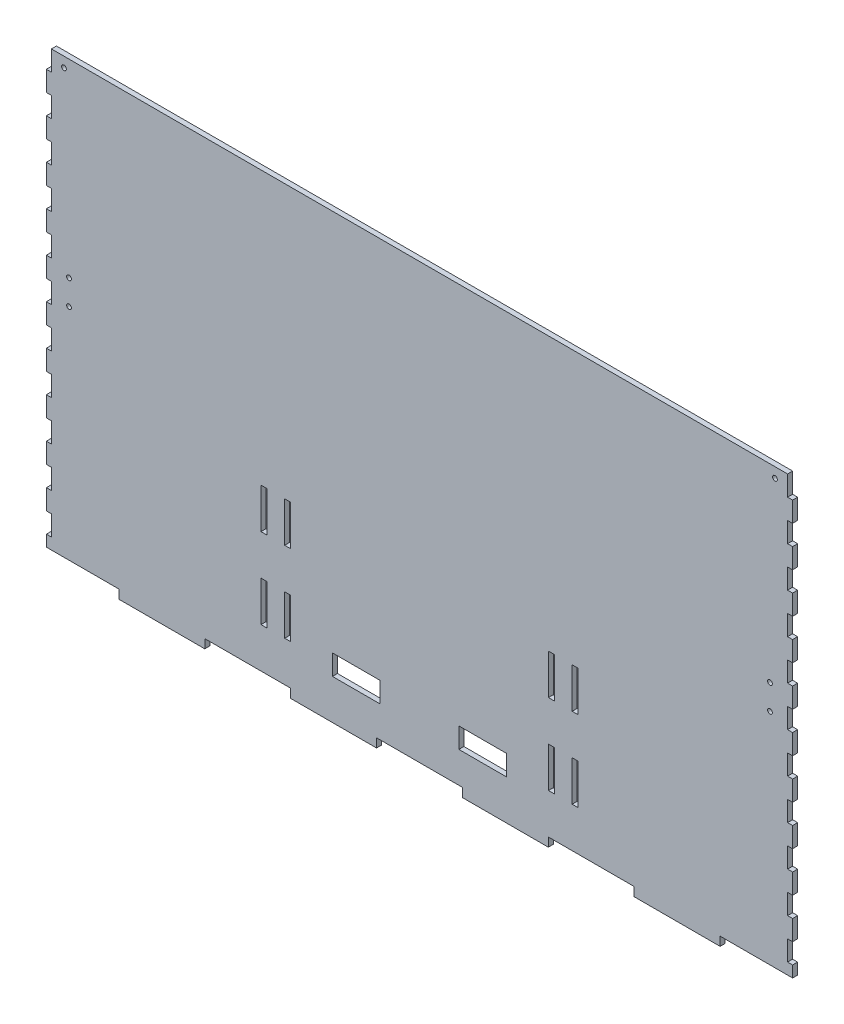
SolidWorks part; units mm, degrees
material "Acrylic (Medium-high impact)"
ref_plane "Front Plane" through (0, 0, 0) normal (0, 0, 1) x (1, 0, 0)
ref_plane "Top Plane" through (0, 0, 0) normal (0, 1, 0) x (1, 0, 0)
ref_plane "Right Plane" through (0, 0, 0) normal (1, 0, 0) x (0, 0, -1)
sketch "Sketch1" plane through (0, 0, 0) normal (0, 0, 1) x (1, 0, 0)
  line L0 (0, 139.7) -> (0, -139.7) construction
  line L1 (-406.4, 139.7) -> (406.4, 139.7)
  line L2 (-406.4, 139.7) -> (-406.4, -139.7)
  line L3 (-406.4, -139.7) -> (406.4, -139.7)
  line L4 (406.4, 139.7) -> (406.4, -139.7)
  line L49 (-381, 127) -> (-381, 114.3)
  line L54 (-381, 139.7) -> (-377.825, 139.7)
  line L55 (-381, 139.7) -> (-381, 127)
  line L56 (-381, 127) -> (-377.825, 127)
  line L57 (-377.825, 139.7) -> (-377.825, 127)
  line L58 (-381, 127) -> (-377.825, 127)
  line L59 (-377.825, 127) -> (-377.825, 114.3)
  line L60 (-381, 114.3) -> (-377.825, 114.3)
  line L61 (-381, 114.3) -> (-381, 101.6)
  line L62 (-381, 114.3) -> (-377.825, 114.3)
  line L63 (-377.825, 114.3) -> (-377.825, 101.6)
  line L64 (-381, 101.6) -> (-377.825, 101.6)
  line L65 (-381, 101.6) -> (-381, 88.9)
  line L66 (-381, 101.6) -> (-377.825, 101.6)
  line L67 (-377.825, 101.6) -> (-377.825, 88.9)
  line L68 (-381, 88.9) -> (-377.825, 88.9)
  line L69 (-381, 88.9) -> (-381, 76.2)
  line L70 (-381, 88.9) -> (-377.825, 88.9)
  line L71 (-377.825, 88.9) -> (-377.825, 76.2)
  line L72 (-381, 76.2) -> (-377.825, 76.2)
  line L73 (-381, 76.2) -> (-381, 63.5)
  line L74 (-381, 76.2) -> (-377.825, 76.2)
  line L75 (-377.825, 76.2) -> (-377.825, 63.5)
  line L76 (-381, 63.5) -> (-377.825, 63.5)
  line L77 (-381, 63.5) -> (-381, 50.8)
  line L78 (-381, 63.5) -> (-377.825, 63.5)
  line L79 (-377.825, 63.5) -> (-377.825, 50.8)
  line L80 (-381, 50.8) -> (-377.825, 50.8)
  line L81 (-381, 50.8) -> (-381, 38.1)
  line L82 (-381, 50.8) -> (-377.825, 50.8)
  line L83 (-377.825, 50.8) -> (-377.825, 38.1)
  line L84 (-381, 38.1) -> (-377.825, 38.1)
  line L85 (-381, 38.1) -> (-381, 25.4)
  line L86 (-381, 38.1) -> (-377.825, 38.1)
  line L87 (-377.825, 38.1) -> (-377.825, 25.4)
  line L88 (-381, 25.4) -> (-377.825, 25.4)
  line L89 (377.825, 127) -> (377.825, 114.3)
  line L90 (377.825, 139.7) -> (381, 139.7)
  line L91 (377.825, 139.7) -> (377.825, 127)
  line L92 (377.825, 127) -> (381, 127)
  line L93 (381, 139.7) -> (381, 127)
  line L94 (377.825, 127) -> (381, 127)
  line L95 (381, 127) -> (381, 114.3)
  line L96 (377.825, 114.3) -> (381, 114.3)
  line L97 (377.825, 114.3) -> (377.825, 101.6)
  line L98 (377.825, 114.3) -> (381, 114.3)
  line L99 (381, 114.3) -> (381, 101.6)
  line L100 (377.825, 101.6) -> (381, 101.6)
  line L101 (377.825, 101.6) -> (377.825, 88.9)
  line L102 (377.825, 101.6) -> (381, 101.6)
  line L103 (381, 101.6) -> (381, 88.9)
  line L104 (377.825, 88.9) -> (381, 88.9)
  line L105 (377.825, 88.9) -> (377.825, 76.2)
  line L106 (377.825, 88.9) -> (381, 88.9)
  line L107 (381, 88.9) -> (381, 76.2)
  line L108 (377.825, 76.2) -> (381, 76.2)
  line L109 (377.825, 76.2) -> (377.825, 63.5)
  line L110 (377.825, 76.2) -> (381, 76.2)
  line L111 (381, 76.2) -> (381, 63.5)
  line L112 (377.825, 63.5) -> (381, 63.5)
  line L113 (377.825, 63.5) -> (377.825, 50.8)
  line L114 (377.825, 63.5) -> (381, 63.5)
  line L115 (381, 63.5) -> (381, 50.8)
  line L116 (377.825, 50.8) -> (381, 50.8)
  line L117 (377.825, 50.8) -> (377.825, 38.1)
  line L118 (377.825, 50.8) -> (381, 50.8)
  line L119 (381, 50.8) -> (381, 38.1)
  line L120 (377.825, 38.1) -> (381, 38.1)
  line L121 (377.825, 38.1) -> (377.825, 25.4)
  line L122 (377.825, 38.1) -> (381, 38.1)
  line L123 (381, 38.1) -> (381, 25.4)
  line L124 (377.825, 25.4) -> (381, 25.4)
  line L125 (-352.2133, -134.112) -> (-352.2133, -139.7)
  line L126 (-406.4, -134.112) -> (-352.2133, -134.112)
  line L127 (-406.4, -134.112) -> (-406.4, -139.7)
  line L128 (-406.4, -139.7) -> (-352.2133, -139.7)
  line L129 (-352.2133, -134.112) -> (-352.2133, -139.7)
  line L130 (-352.2133, -134.112) -> (-298.0267, -134.112)
  line L131 (-298.0267, -134.112) -> (-298.0267, -139.7)
  line L132 (-352.2133, -139.7) -> (-298.0267, -139.7)
  line L133 (-298.0267, -134.112) -> (-298.0267, -139.7)
  line L134 (-298.0267, -134.112) -> (-243.84, -134.112)
  line L135 (-243.84, -134.112) -> (-243.84, -139.7)
  line L136 (-298.0267, -139.7) -> (-243.84, -139.7)
  line L137 (-243.84, -134.112) -> (-243.84, -139.7)
  line L138 (-243.84, -134.112) -> (-189.6533, -134.112)
  line L139 (-189.6533, -134.112) -> (-189.6533, -139.7)
  line L140 (-243.84, -139.7) -> (-189.6533, -139.7)
  line L141 (-189.6533, -134.112) -> (-189.6533, -139.7)
  line L142 (-189.6533, -134.112) -> (-135.4667, -134.112)
  line L143 (-135.4667, -134.112) -> (-135.4667, -139.7)
  line L144 (-189.6533, -139.7) -> (-135.4667, -139.7)
  line L145 (-135.4667, -134.112) -> (-135.4667, -139.7)
  line L146 (-135.4667, -134.112) -> (-81.28, -134.112)
  line L147 (-81.28, -134.112) -> (-81.28, -139.7)
  line L148 (-135.4667, -139.7) -> (-81.28, -139.7)
  line L149 (-81.28, -134.112) -> (-81.28, -139.7)
  line L150 (-81.28, -134.112) -> (-27.0933, -134.112)
  line L151 (-27.0933, -134.112) -> (-27.0933, -139.7)
  line L152 (-81.28, -139.7) -> (-27.0933, -139.7)
  line L153 (-27.0933, -134.112) -> (-27.0933, -139.7)
  line L154 (-27.0933, -134.112) -> (27.0933, -134.112)
  line L155 (27.0933, -134.112) -> (27.0933, -139.7)
  line L156 (-27.0933, -139.7) -> (27.0933, -139.7)
  line L157 (27.0933, -134.112) -> (27.0933, -139.7)
  line L158 (27.0933, -134.112) -> (81.28, -134.112)
  line L159 (81.28, -134.112) -> (81.28, -139.7)
  line L160 (27.0933, -139.7) -> (81.28, -139.7)
  line L161 (81.28, -134.112) -> (81.28, -139.7)
  line L162 (81.28, -134.112) -> (135.4667, -134.112)
  line L163 (135.4667, -134.112) -> (135.4667, -139.7)
  line L164 (81.28, -139.7) -> (135.4667, -139.7)
  line L165 (135.4667, -134.112) -> (135.4667, -139.7)
  line L166 (135.4667, -134.112) -> (189.6533, -134.112)
  line L167 (189.6533, -134.112) -> (189.6533, -139.7)
  line L168 (135.4667, -139.7) -> (189.6533, -139.7)
  line L169 (189.6533, -134.112) -> (189.6533, -139.7)
  line L170 (189.6533, -134.112) -> (243.84, -134.112)
  line L171 (243.84, -134.112) -> (243.84, -139.7)
  line L172 (189.6533, -139.7) -> (243.84, -139.7)
  line L173 (243.84, -134.112) -> (243.84, -139.7)
  line L174 (243.84, -134.112) -> (298.0267, -134.112)
  line L175 (298.0267, -134.112) -> (298.0267, -139.7)
  line L176 (243.84, -139.7) -> (298.0267, -139.7)
  line L177 (298.0267, -134.112) -> (298.0267, -139.7)
  line L178 (298.0267, -134.112) -> (352.2133, -134.112)
  line L179 (352.2133, -134.112) -> (352.2133, -139.7)
  line L180 (298.0267, -139.7) -> (352.2133, -139.7)
  line L181 (352.2133, -134.112) -> (352.2133, -139.7)
  line L182 (352.2133, -134.112) -> (406.4, -134.112)
  line L183 (406.4, -134.112) -> (406.4, -139.7)
  line L184 (352.2133, -139.7) -> (406.4, -139.7)
  line L205 (-90.678, 84.5227) -> (-90.678, -139.7) construction
  line L206 (90.678, 84.5227) -> (90.678, -139.7) construction
  line L207 (-90.678, -27.5886) -> (90.678, -27.5886) construction
  line L208 (-381, 25.4) -> (-381, 12.7)
  line L209 (-381, 25.4) -> (-377.825, 25.4)
  line L210 (-377.825, 25.4) -> (-377.825, 12.7)
  line L211 (-381, 12.7) -> (-377.825, 12.7)
  line L212 (-381, 12.7) -> (-381, 0)
  line L213 (-381, 12.7) -> (-377.825, 12.7)
  line L214 (-377.825, 12.7) -> (-377.825, 0)
  line L215 (-381, 0) -> (-377.825, 0)
  line L224 (-377.825, 0) -> (377.825, 0) construction
  line L229 (377.825, 25.4) -> (377.825, 12.7)
  line L230 (377.825, 25.4) -> (381, 25.4)
  line L231 (381, 25.4) -> (381, 12.7)
  line L232 (377.825, 12.7) -> (381, 12.7)
  line L233 (377.825, 12.7) -> (377.825, 0)
  line L234 (377.825, 12.7) -> (381, 12.7)
  line L235 (381, 12.7) -> (381, 0)
  line L236 (377.825, 0) -> (381, 0)
  line L237 (-381, 0) -> (-381, -12.7)
  line L238 (-381, 0) -> (-377.825, 0)
  line L239 (-377.825, 0) -> (-377.825, -12.7)
  line L240 (-381, -12.7) -> (-377.825, -12.7)
  line L241 (-381, -12.7) -> (-381, -25.4)
  line L242 (-381, -12.7) -> (-377.825, -12.7)
  line L243 (-377.825, -12.7) -> (-377.825, -25.4)
  line L244 (-381, -25.4) -> (-377.825, -25.4)
  line L245 (-381, -25.4) -> (-381, -38.1)
  line L246 (-381, -25.4) -> (-377.825, -25.4)
  line L247 (-377.825, -25.4) -> (-377.825, -38.1)
  line L248 (-381, -38.1) -> (-377.825, -38.1)
  line L249 (-381, -38.1) -> (-381, -50.8)
  line L250 (-381, -38.1) -> (-377.825, -38.1)
  line L251 (-377.825, -38.1) -> (-377.825, -50.8)
  line L252 (-381, -50.8) -> (-377.825, -50.8)
  line L253 (-381, -50.8) -> (-381, -63.5)
  line L254 (-381, -50.8) -> (-377.825, -50.8)
  line L255 (-377.825, -50.8) -> (-377.825, -63.5)
  line L256 (-381, -63.5) -> (-377.825, -63.5)
  line L257 (-381, -63.5) -> (-381, -76.2)
  line L258 (-381, -63.5) -> (-377.825, -63.5)
  line L259 (-377.825, -63.5) -> (-377.825, -76.2)
  line L260 (-381, -76.2) -> (-377.825, -76.2)
  line L261 (-381, -76.2) -> (-381, -88.9)
  line L262 (-381, -76.2) -> (-377.825, -76.2)
  line L263 (-377.825, -76.2) -> (-377.825, -88.9)
  line L264 (-381, -88.9) -> (-377.825, -88.9)
  line L265 (-381, -88.9) -> (-381, -101.6)
  line L266 (-381, -88.9) -> (-377.825, -88.9)
  line L267 (-377.825, -88.9) -> (-377.825, -101.6)
  line L268 (-381, -101.6) -> (-377.825, -101.6)
  line L269 (-381, -101.6) -> (-381, -114.3)
  line L270 (-381, -101.6) -> (-377.825, -101.6)
  line L271 (-377.825, -101.6) -> (-377.825, -114.3)
  line L272 (-381, -114.3) -> (-377.825, -114.3)
  line L273 (-381, -114.3) -> (-381, -127)
  line L274 (-381, -114.3) -> (-377.825, -114.3)
  line L275 (-377.825, -114.3) -> (-377.825, -127)
  line L276 (-381, -127) -> (-377.825, -127)
  line L277 (-381, -127) -> (-381, -139.7)
  line L278 (-381, -127) -> (-377.825, -127)
  line L279 (-377.825, -127) -> (-377.825, -139.7)
  line L280 (-381, -139.7) -> (-377.825, -139.7)
  line L281 (377.825, 0) -> (377.825, -12.7)
  line L282 (377.825, 0) -> (381, 0)
  line L283 (381, 0) -> (381, -12.7)
  line L284 (377.825, -12.7) -> (381, -12.7)
  line L285 (377.825, -12.7) -> (377.825, -25.4)
  line L286 (377.825, -12.7) -> (381, -12.7)
  line L287 (381, -12.7) -> (381, -25.4)
  line L288 (377.825, -25.4) -> (381, -25.4)
  line L289 (377.825, -25.4) -> (377.825, -38.1)
  line L290 (377.825, -25.4) -> (381, -25.4)
  line L291 (381, -25.4) -> (381, -38.1)
  line L292 (377.825, -38.1) -> (381, -38.1)
  line L293 (377.825, -38.1) -> (377.825, -50.8)
  line L294 (377.825, -38.1) -> (381, -38.1)
  line L295 (381, -38.1) -> (381, -50.8)
  line L296 (377.825, -50.8) -> (381, -50.8)
  line L297 (377.825, -50.8) -> (377.825, -63.5)
  line L298 (377.825, -50.8) -> (381, -50.8)
  line L299 (381, -50.8) -> (381, -63.5)
  line L300 (377.825, -63.5) -> (381, -63.5)
  line L301 (377.825, -63.5) -> (377.825, -76.2)
  line L302 (377.825, -63.5) -> (381, -63.5)
  line L303 (381, -63.5) -> (381, -76.2)
  line L304 (377.825, -76.2) -> (381, -76.2)
  line L305 (377.825, -76.2) -> (377.825, -88.9)
  line L306 (377.825, -76.2) -> (381, -76.2)
  line L307 (381, -76.2) -> (381, -88.9)
  line L308 (377.825, -88.9) -> (381, -88.9)
  line L309 (377.825, -88.9) -> (377.825, -101.6)
  line L310 (377.825, -88.9) -> (381, -88.9)
  line L311 (381, -88.9) -> (381, -101.6)
  line L312 (377.825, -101.6) -> (381, -101.6)
  line L313 (377.825, -101.6) -> (377.825, -114.3)
  line L314 (377.825, -101.6) -> (381, -101.6)
  line L315 (381, -101.6) -> (381, -114.3)
  line L316 (377.825, -114.3) -> (381, -114.3)
  line L317 (377.825, -114.3) -> (377.825, -127)
  line L318 (377.825, -114.3) -> (381, -114.3)
  line L319 (381, -114.3) -> (381, -127)
  line L320 (377.825, -127) -> (381, -127)
  line L321 (377.825, -127) -> (377.825, -139.7)
  line L322 (377.825, -127) -> (381, -127)
  line L323 (381, -127) -> (381, -139.7)
  line L324 (377.825, -139.7) -> (381, -139.7)
  point P6 (0, 0)
  point P128 (0, -27.5886)
  point P153 (0, 0)
  dimension "D4" = 12.7
  dimension "D5" = 3.175
  dimension "D10" = 181.356
  dimension "D12" = 755.65
  dimension "D8" = 812.8
  dimension "D11" = 54.1867
  dimension "D2" = 273.812
  dimension "D9" = 279.4
  dimension "D3" = 22
  dimension "D7" = 15
  dimension "D6" = 22
extrude "Main Extrude" add sketch "Sketch1" along normal blind 3.175 contours L321 L317 L313 L309 L305 L301 L297 L293 L289 L285 L281 L233 L229 L121 L117 L113 L109 L105 L101 L97 L89 L91 L1 L57 L59 L63 L67 L71 L75 L79 L83 L87 L210 L214 L239 L243 L247 L251 L255 L259 L263 L267 L271 L275 L279 L126 L130 L134 L138 L142 L146 | L277 L273 L269 L265 L261 L257 L253 L249 L245 L241 L237 L212 L208 L85 L81 L77 L73 L69 L65 L61 L49 L55 L1 L2 L126 | L319 L323 L182 L4 L1 L93 L95 L99 L103 L107 L111 L115 L119 L123 L231 L235 L283 L287 L291 L295 L299 L303 L307 L311 L315 | L126 L279 L3 L125 | L135 L134 L131 L3 | L143 L142 L139 L3 | L151 L150 L147 L3 | L159 L158 L155 L3 | L167 L166 L163 L3 | L175 L174 L171 L3 | L323 L182 L321 L184 | L89 L96 L95 L92 | L101 L104 L103 L100 | L109 L112 L111 L108 | L117 L120 L119 L116 | L229 L232 L231 L124 | L281 L284 L283 L236 | L289 L292 L291 L288 | L297 L300 L299 L296 | L305 L308 L307 L304 | L313 L316 L315 L312 | L323 L320 L321 L182 | L49 L60 L59 L56 | L65 L68 L67 L64 | L73 L76 L75 L72 | L81 L84 L83 L80 | L208 L211 L210 L88 | L237 L240 L239 L215 | L245 L248 L247 L244 | L253 L256 L255 L252 | L261 L264 L263 L260 | L269 L272 L271 L268 | L279 L276 L277 L126 | L277 L126 L2 L3 | L321 L182 L179 L3 | L182 L323 L3 L4 | L279 L126 L277 L128 region at (-393.7, 2.794, 0) region at (-393.7, -136.906, 0) region at (0, 2.794, 0) region at (-379.4125, 120.65, 0) region at (-379.4125, -130.556, 0) region at (-379.4125, -136.906, 0) region at (-365.0192, -136.906, 0) region at (393.7, 2.794, 0) region at (379.4125, 120.65, 0) region at (-379.4125, 95.25, 0) region at (-379.4125, -107.95, 0) region at (-270.9333, -136.906, 0) region at (393.7, -136.906, 0) region at (379.4125, 95.25, 0) region at (-379.4125, 69.85, 0) region at (-379.4125, -82.55, 0) region at (379.4125, -136.906, 0) region at (379.4125, -130.556, 0) region at (-162.56, -136.906, 0) region at (365.0192, -136.906, 0) region at (379.4125, 69.85, 0) region at (-379.4125, 44.45, 0) region at (-379.4125, -57.15, 0) region at (379.4125, -107.95, 0) region at (-54.1867, -136.906, 0) region at (270.9333, -136.906, 0) region at (379.4125, 44.45, 0) region at (-379.4125, 19.05, 0) region at (-379.4125, -31.75, 0) region at (379.4125, -82.55, 0) region at (54.1867, -136.906, 0) region at (162.56, -136.906, 0) region at (379.4125, 19.05, 0) region at (-379.4125, -6.35, 0) region at (379.4125, -57.15, 0) region at (379.4125, -6.35, 0) region at (379.4125, -31.75, 0)
sketch "Sketch8" plane through (0, 0, 3.175) normal (0, 0, 1) x (1, 0, 0)
  line L0 (-406.4, 139.7) -> (-406.4, -139.7) construction
  line L1 (-381, 28.2575) -> (-384.175, 28.2575)
  line L2 (-381, 28.2575) -> (-381, -3.6195)
  line L3 (-381, -3.6195) -> (-384.175, -3.6195)
  line L4 (-384.175, 28.2575) -> (-384.175, -3.6195)
  line L5 (-406.4, -139.7) -> (-352.2133, -139.7) construction
  line L6 (381, 28.2575) -> (384.175, 28.2575)
  line L7 (381, 28.2575) -> (381, -3.6195)
  line L8 (381, -3.6195) -> (384.175, -3.6195)
  line L9 (384.175, 28.2575) -> (384.175, -3.6195)
  line L11 (-381, 88.9) -> (-381, 76.2) construction
  line L12 (-352.2133, -134.112) -> (-298.0267, -134.112) construction
  line L13 (381, 88.9) -> (381, 76.2) construction
  line L14 (-393.7, -120.65) -> (393.7, -120.65) construction
  circle A0 centre (-393.7, -120.65) radius 1.5
  circle A1 centre (393.7, -120.65) radius 1.5
  point P6 (0, -120.65)
  point P16 (-384.175, 12.319)
  dimension "D5" = 3
  dimension "D1" = 31.877
  dimension "D2" = 3.175
  dimension "D3" = 146.431
  dimension "D4" = 19.05
  dimension "D6" = 12.7
extrude "Mount Holes" cut sketch "Sketch8" against normal through all
sketch "Sketch3" plane through (0, 0, 3.175) normal (0, 0, 1) x (1, 0, 0)
  line L0 (-135.4667, -134.112) -> (-81.28, -134.112) construction
  line L1 (-96.52, 126.492) -> (-84.836, 126.492)
  line L2 (-96.52, 126.492) -> (-96.52, -134.112)
  line L3 (-96.52, -134.112) -> (-84.836, -134.112)
  line L4 (-84.836, 126.492) -> (-84.836, -134.112)
  line L5 (81.28, -134.112) -> (135.4667, -134.112) construction
  line L6 (84.836, 126.492) -> (96.52, 126.492)
  line L7 (84.836, 126.492) -> (84.836, -134.112)
  line L8 (84.836, -134.112) -> (96.52, -134.112)
  line L9 (96.52, 126.492) -> (96.52, -134.112)
  line L10 (-84.836, -3.81) -> (84.836, -3.81) construction
  line L12 (-106.553, 10.3505) -> (-74.803, 10.3505)
  line L13 (-106.553, 10.3505) -> (-106.553, 0.8255)
  line L14 (-106.553, 0.8255) -> (-74.803, 0.8255)
  line L15 (-74.803, 10.3505) -> (-74.803, 0.8255)
  line L16 (74.803, 10.3505) -> (106.553, 10.3505)
  line L17 (74.803, 10.3505) -> (74.803, 0.8255)
  line L18 (74.803, 0.8255) -> (106.553, 0.8255)
  line L19 (106.553, 10.3505) -> (106.553, 0.8255)
  line L20 (-96.52, 126.492) -> (-92.6465, 126.492)
  line L21 (-96.52, 126.492) -> (-96.52, 82.042)
  line L22 (-96.52, 82.042) -> (-92.6465, 82.042)
  line L23 (-92.6465, 126.492) -> (-92.6465, 82.042)
  line L24 (-84.836, 126.492) -> (-88.7095, 126.492)
  line L25 (-84.836, 126.492) -> (-84.836, 82.042)
  line L26 (-84.836, 82.042) -> (-88.7095, 82.042)
  line L27 (-88.7095, 126.492) -> (-88.7095, 82.042)
  line L28 (84.836, 126.492) -> (88.7095, 126.492)
  line L29 (84.836, 126.492) -> (84.836, 82.042)
  line L30 (84.836, 82.042) -> (88.7095, 82.042)
  line L31 (88.7095, 126.492) -> (88.7095, 82.042)
  line L32 (96.52, 126.492) -> (92.6465, 126.492)
  line L33 (96.52, 126.492) -> (96.52, 82.042)
  line L34 (96.52, 82.042) -> (92.6465, 82.042)
  line L35 (92.6465, 126.492) -> (92.6465, 82.042)
  point P14 (-90.678, 126.492)
  point P15 (90.678, 126.492)
  point P16 (0, -3.81)
  point P27 (-90.678, 10.3505)
  point P28 (90.678, 10.3505)
  point P29 (-74.803, 5.588)
  dimension "D1" = 11.684
  dimension "D2" = 260.604
  dimension "D3" = 181.356
  dimension "D4" = 9.525
  dimension "D5" = 139.7
  dimension "D6" = 31.75
  dimension "D8" = 3.937
  dimension "D7" = 44.45
extrude "Door Slots" [suppressed] cut sketch "Sketch3" against normal through all contours L2 L12 L4 L1 | L2 L14 L4 L12 | L15 L12 L4 L14 | L13 L14 L2 L12 | L14 L2 L3 L4 | L7 L16 L9 L6 | L7 L18 L9 L16 | L19 L16 L9 L18 | L17 L18 L7 L16 | L18 L7 L8 L9
sketch "Sketch4" plane through (0, 0, 0) normal (0, 0, 1) x (1, 0, 0)
  line L1 (-81.28, -139.7) -> (-27.0933, -139.7) construction
  line L2 (-55.48, -112.41) -> (-52.178, -112.41)
  line L3 (-52.178, -112.41) -> (-52.178, -106.172)
  line L4 (-52.178, -106.172) -> (-2.178, -106.172)
  line L5 (-2.178, -106.172) -> (-2.178, -112.41)
  line L6 (-2.178, -112.41) -> (1.124, -112.41)
  line L9 (-55.48, -112.41) -> (-55.48, -134.112)
  line L10 (-55.48, -134.112) -> (-52.178, -134.112)
  line L11 (-52.178, -134.112) -> (-52.178, -139.7)
  line L12 (1.124, -112.41) -> (1.124, -134.112)
  line L13 (1.124, -134.112) -> (-2.178, -134.112)
  line L14 (-2.178, -134.112) -> (-2.178, -139.7)
  line L15 (-52.178, -139.7) -> (-2.178, -139.7)
  line L16 (-27.0933, -134.112) -> (27.0933, -134.112) construction
  line L17 (-27.0933, -134.112) -> (27.0933, -134.112) construction
  line L18 (12.128, -101.642) -> (42.228, -101.642)
  line L19 (12.128, -101.642) -> (12.128, -114.492)
  line L20 (12.128, -114.492) -> (42.228, -114.492)
  line L21 (42.228, -101.642) -> (42.228, -114.492)
  line L24 (-96.52, -134.112) -> (-84.836, -134.112) construction
  line L25 (84.836, -134.112) -> (96.52, -134.112) construction
  point P9 (-27.178, -106.172)
  point P10 (-27.178, -139.7)
  point P22 (27.178, -114.492)
  point P25 (90.678, -134.112)
  point P26 (12.128, -108.067)
  point P30 (-90.678, -134.112)
  dimension "D1" = 50
  dimension "D2" = 3.302
  dimension "D4" = 21.702
  dimension "D5" = 30.1
  dimension "D6" = 12.85
  dimension "D9" = 63.5
  dimension "D8" = 63.5
  dimension "D3" = 27.94
  dimension "D7" = 26.045
extrude "Trough and Lever Holes" [suppressed] cut sketch "Sketch4" along normal through all contours L11 L15 L14 L13 L12 L6 L5 L4 L3 L2 L9 L10 | L21 L18 L19 L20
sketch "Sketch5" plane through (0, 0, 3.175) normal (0, 0, 1) x (1, 0, 0)
  line L0 (-90.678, 126.492) -> (-90.678, -134.112) construction
  line L1 (-96.52, 126.492) -> (-84.836, 126.492) construction
  line L2 (-96.52, -134.112) -> (-84.836, -134.112) construction
  line L3 (90.678, 126.492) -> (90.678, -134.112) construction
  line L4 (84.836, 126.492) -> (96.52, 126.492) construction
  line L5 (84.836, -134.112) -> (96.52, -134.112) construction
  line L6 (-135.4667, -134.112) -> (-81.28, -134.112) construction
  line L19 (-99.998, -134.112) -> (-96.3199, -134.112)
  line L20 (-99.998, -134.112) -> (-99.998, -108.712)
  line L21 (-99.998, -108.712) -> (-96.3199, -108.712)
  line L22 (-96.3199, -134.112) -> (-96.3199, -108.712)
  line L24 (-99.998, -108.712) -> (-96.3199, -108.712)
  line L25 (-99.998, -108.712) -> (-99.998, -83.312)
  line L26 (-99.998, -83.312) -> (-96.3199, -83.312)
  line L27 (-96.3199, -108.712) -> (-96.3199, -83.312)
  line L28 (-96.3199, -83.312) -> (-99.998, -83.312)
  line L29 (-96.3199, -83.312) -> (-96.3199, -57.912)
  line L30 (-96.3199, -57.912) -> (-99.998, -57.912)
  line L31 (-99.998, -83.312) -> (-99.998, -57.912)
  line L32 (-99.998, -57.912) -> (-96.3199, -57.912)
  line L33 (-99.998, -57.912) -> (-99.998, -32.512)
  line L34 (-99.998, -32.512) -> (-96.3199, -32.512)
  line L35 (-96.3199, -57.912) -> (-96.3199, -32.512)
  line L36 (-96.3199, -32.512) -> (-99.998, -32.512)
  line L37 (-96.3199, -32.512) -> (-96.3199, -7.112)
  line L38 (-96.3199, -7.112) -> (-99.998, -7.112)
  line L39 (-99.998, -32.512) -> (-99.998, -7.112)
  line L40 (-81.358, -108.712) -> (-85.0361, -108.712)
  line L41 (-85.0361, -134.112) -> (-85.0361, -108.712)
  line L42 (-81.358, -134.112) -> (-85.0361, -134.112)
  line L43 (-81.358, -134.112) -> (-81.358, -108.712)
  line L44 (-81.358, -83.312) -> (-85.0361, -83.312)
  line L45 (-85.0361, -108.712) -> (-85.0361, -83.312)
  line L46 (-81.358, -108.712) -> (-85.0361, -108.712)
  line L47 (-81.358, -108.712) -> (-81.358, -83.312)
  line L48 (-85.0361, -57.912) -> (-81.358, -57.912)
  line L49 (-81.358, -83.312) -> (-81.358, -57.912)
  line L50 (-85.0361, -83.312) -> (-81.358, -83.312)
  line L51 (-85.0361, -83.312) -> (-85.0361, -57.912)
  line L52 (-81.358, -32.512) -> (-85.0361, -32.512)
  line L53 (-85.0361, -57.912) -> (-85.0361, -32.512)
  line L54 (-81.358, -57.912) -> (-85.0361, -57.912)
  line L55 (-81.358, -57.912) -> (-81.358, -32.512)
  line L56 (-85.0361, -7.112) -> (-81.358, -7.112)
  line L57 (-81.358, -32.512) -> (-81.358, -7.112)
  line L58 (-85.0361, -32.512) -> (-81.358, -32.512)
  line L59 (-85.0361, -32.512) -> (-85.0361, -7.112)
  line L60 (0, -1.7463) -> (0, 1.7463) construction
  line L61 (99.998, -108.712) -> (96.3199, -108.712)
  line L62 (96.3199, -134.112) -> (96.3199, -108.712)
  line L63 (99.998, -134.112) -> (96.3199, -134.112)
  line L64 (99.998, -134.112) -> (99.998, -108.712)
  line L65 (99.998, -83.312) -> (96.3199, -83.312)
  line L66 (96.3199, -108.712) -> (96.3199, -83.312)
  line L67 (99.998, -108.712) -> (96.3199, -108.712)
  line L68 (99.998, -108.712) -> (99.998, -83.312)
  line L69 (96.3199, -57.912) -> (99.998, -57.912)
  line L70 (99.998, -83.312) -> (99.998, -57.912)
  line L71 (96.3199, -83.312) -> (99.998, -83.312)
  line L72 (96.3199, -83.312) -> (96.3199, -57.912)
  line L73 (99.998, -32.512) -> (96.3199, -32.512)
  line L74 (96.3199, -57.912) -> (96.3199, -32.512)
  line L75 (99.998, -57.912) -> (96.3199, -57.912)
  line L76 (99.998, -57.912) -> (99.998, -32.512)
  line L77 (96.3199, -7.112) -> (99.998, -7.112)
  line L78 (99.998, -32.512) -> (99.998, -7.112)
  line L79 (96.3199, -32.512) -> (99.998, -32.512)
  line L80 (96.3199, -32.512) -> (96.3199, -7.112)
  line L81 (85.0361, -32.512) -> (85.0361, -7.112)
  line L82 (85.0361, -32.512) -> (81.358, -32.512)
  line L83 (81.358, -32.512) -> (81.358, -7.112)
  line L84 (85.0361, -7.112) -> (81.358, -7.112)
  line L85 (81.358, -57.912) -> (81.358, -32.512)
  line L86 (81.358, -57.912) -> (85.0361, -57.912)
  line L87 (85.0361, -57.912) -> (85.0361, -32.512)
  line L88 (81.358, -32.512) -> (85.0361, -32.512)
  line L89 (85.0361, -83.312) -> (85.0361, -57.912)
  line L90 (85.0361, -83.312) -> (81.358, -83.312)
  line L91 (81.358, -83.312) -> (81.358, -57.912)
  line L92 (85.0361, -57.912) -> (81.358, -57.912)
  line L93 (81.358, -108.712) -> (81.358, -83.312)
  line L94 (81.358, -108.712) -> (85.0361, -108.712)
  line L95 (85.0361, -108.712) -> (85.0361, -83.312)
  line L96 (81.358, -83.312) -> (85.0361, -83.312)
  line L97 (81.358, -134.112) -> (81.358, -108.712)
  line L98 (81.358, -134.112) -> (85.0361, -134.112)
  line L99 (85.0361, -134.112) -> (85.0361, -108.712)
  line L100 (81.358, -108.712) -> (85.0361, -108.712)
  dimension "D1" = 25.4
  dimension "D3" = 5.6419
  dimension "D2" = 9.32
extrude "Door Guide Slots" cut sketch "Sketch5" against normal through all contours L21 L27 L26 L25 | L30 L35 L34 L33 | L48 L55 L52 L53 | L40 L47 L44 L45 | L86 L87 L82 L85 | L94 L95 L90 L93 | L69 L76 L73 L74 | L61 L68 L65 L66 region at (-98.1589, -96.012, 3.175) region at (-98.1589, -45.212, 3.175) region at (-83.1971, -96.012, 3.175) region at (-83.1971, -45.212, 3.175) region at (98.1589, -96.012, 3.175) region at (98.1589, -45.212, 3.175) region at (83.1971, -45.212, 3.175) region at (83.1971, -96.012, 3.175)
sketch "Sketch7" plane through (0, 0, 3.175) normal (0, 0, 1) x (1, 0, 0)
  line L0 (-24.828, -108.067) -> (24.828, -108.067) construction
  line L1 (-54.928, -101.642) -> (-24.828, -101.642)
  line L2 (-54.928, -101.642) -> (-54.928, -114.492)
  line L3 (-54.928, -114.492) -> (-24.828, -114.492)
  line L4 (-24.828, -101.642) -> (-24.828, -114.492)
  line L5 (54.928, -101.642) -> (24.828, -101.642)
  line L6 (54.928, -101.642) -> (54.928, -114.492)
  line L7 (54.928, -114.492) -> (24.828, -114.492)
  line L8 (24.828, -101.642) -> (24.828, -114.492)
  line L9 (0, -108.067) -> (0, 0) construction
  line L10 (-96.52, -134.112) -> (-84.836, -134.112) construction
  line L12 (-135.4667, -134.112) -> (-81.28, -134.112) construction
  point P12 (-54.928, -108.067)
  point P15 (-39.878, -101.642)
  point P18 (-90.678, -134.112)
  dimension "D1" = 12.85
  dimension "D2" = 30.1
  dimension "D3" = 50.8
  dimension "D4" = 26.045
extrude "Lever Holes" cut sketch "Sketch7" against normal through all
sketch "Sketch10" [suppressed] plane through (0, 0, 3.175) normal (0, 0, 1) x (1, 0, 0)
  line L0 (-101.678, 127.492) -> (-79.678, 127.492) construction
  line L2 (-92.6465, 126.492) -> (-88.7095, 126.492) construction
  line L3 (-90.678, 127.492) -> (-90.678, 126.492) construction
  line L4 (79.678, 127.492) -> (101.678, 127.492) construction
  line L5 (90.678, 127.492) -> (90.678, 126.492) construction
  line L6 (88.7095, 126.492) -> (92.6465, 126.492) construction
  circle A0 centre (-101.678, 127.492) radius 1.5
  circle A1 centre (-79.678, 127.492) radius 1.5
  circle A2 centre (79.678, 127.492) radius 1.5
  circle A3 centre (101.678, 127.492) radius 1.5
  dimension "D1" = 3
  dimension "D2" = 22
  dimension "D3" = 1
extrude "Door Guide Mount Holes" [suppressed] cut sketch "Sketch10" against normal through all
sketch "Sketch12" plane through (0, 0, 3.175) normal (0, 0, 1) x (1, 0, 0)
  line L0 (-246.507, 20.193) -> (-246.507, 4.445) construction
  line L1 (-221.107, 20.193) -> (-221.107, 4.445) construction
  line L2 (-246.507, 20.193) -> (-221.107, 20.193) construction
  line L3 (-246.507, 4.445) -> (-221.107, 4.445) construction
  line L4 (-243.332, 133.35) -> (-224.282, 133.35) construction
  line L5 (-406.4, 139.7) -> (406.4, 139.7) construction
  line L6 (-233.807, 20.193) -> (-233.807, 133.35) construction
  line L7 (-243.84, -134.112) -> (-189.6533, -134.112) construction
  line L8 (0, -1.7463) -> (0, 1.7463) construction
  line L9 (233.807, 20.193) -> (233.807, 133.35) construction
  line L10 (243.332, 133.35) -> (224.282, 133.35) construction
  line L11 (246.507, 4.445) -> (221.107, 4.445) construction
  line L12 (246.507, 20.193) -> (221.107, 20.193) construction
  line L13 (221.107, 20.193) -> (221.107, 4.445) construction
  line L14 (246.507, 20.193) -> (246.507, 4.445) construction
  circle A0 centre (-246.507, 20.193) radius 1.5
  circle A1 centre (-246.507, 4.445) radius 1.5
  circle A2 centre (-221.107, 4.445) radius 1.5
  circle A3 centre (-221.107, 20.193) radius 1.5
  circle A4 centre (-243.332, 133.35) radius 1.5
  circle A5 centre (-224.282, 133.35) radius 1.5
  circle A6 centre (224.282, 133.35) radius 1.5
  circle A7 centre (243.332, 133.35) radius 1.5
  circle A8 centre (221.107, 20.193) radius 1.5
  circle A9 centre (221.107, 4.445) radius 1.5
  circle A10 centre (246.507, 4.445) radius 1.5
  circle A11 centre (246.507, 20.193) radius 1.5
  point P12 (-233.807, 133.35)
  dimension "D1" = 3
  dimension "D2" = 233.807
  dimension "D3" = 19.05
  dimension "D4" = 6.35
  dimension "D5" = 25.4
  dimension "D6" = 15.748
  dimension "D7" = 138.557
extrude "Extension Clip Holes" cut sketch "Sketch12" against normal through all
sketch "Sketch11" plane through (0, 0, 3.175) normal (0, 0, 1) x (1, 0, 0)
  line L0 (-232.2195, 139.7) -> (-232.2195, 127)
  line L1 (-232.2195, 127) -> (-235.3945, 127)
  line L2 (-235.3945, 127) -> (-235.3945, 114.3)
  line L3 (-235.3945, 114.3) -> (-232.2195, 114.3)
  line L4 (232.2195, 139.7) -> (232.2195, 127)
  line L5 (232.2195, 127) -> (235.3945, 127)
  line L6 (235.3945, 127) -> (235.3945, 114.3)
  line L7 (235.3945, 114.3) -> (232.2195, 114.3)
  line L9 (-381, 127) -> (-377.825, 127) construction
  line L10 (-377.825, 139.7) -> (-377.825, 127) construction
  line L11 (235.3945, 120.65) -> (-235.3945, 120.65) construction
  line L12 (-232.2195, 114.3) -> (-232.2195, 101.6)
  line L13 (-232.2195, 101.6) -> (-235.3945, 101.6)
  line L14 (-235.3945, 101.6) -> (-235.3945, 88.9)
  line L15 (-235.3945, 88.9) -> (-232.2195, 88.9)
  line L16 (232.2195, 114.3) -> (232.2195, 101.6)
  line L17 (232.2195, 101.6) -> (235.3945, 101.6)
  line L18 (235.3945, 101.6) -> (235.3945, 88.9)
  line L19 (235.3945, 88.9) -> (232.2195, 88.9)
  line L20 (-232.2195, 88.9) -> (-232.2195, 76.2)
  line L21 (-232.2195, 76.2) -> (-235.3945, 76.2)
  line L22 (-235.3945, 76.2) -> (-235.3945, 63.5)
  line L23 (-235.3945, 63.5) -> (-232.2195, 63.5)
  line L24 (232.2195, 88.9) -> (232.2195, 76.2)
  line L25 (232.2195, 76.2) -> (235.3945, 76.2)
  line L26 (235.3945, 76.2) -> (235.3945, 63.5)
  line L27 (235.3945, 63.5) -> (232.2195, 63.5)
  line L28 (-232.2195, 63.5) -> (-232.2195, 50.8)
  line L29 (-232.2195, 50.8) -> (-235.3945, 50.8)
  line L30 (-235.3945, 50.8) -> (-235.3945, 38.1)
  line L31 (-235.3945, 38.1) -> (-232.2195, 38.1)
  line L32 (232.2195, 63.5) -> (232.2195, 50.8)
  line L33 (232.2195, 50.8) -> (235.3945, 50.8)
  line L34 (235.3945, 50.8) -> (235.3945, 38.1)
  line L35 (235.3945, 38.1) -> (232.2195, 38.1)
  line L36 (-232.2195, 38.1) -> (-232.2195, 25.4)
  line L37 (-232.2195, 25.4) -> (-235.3945, 25.4)
  line L38 (-235.3945, 25.4) -> (-235.3945, 12.7)
  line L39 (-235.3945, 12.7) -> (-232.2195, 12.7)
  line L40 (232.2195, 38.1) -> (232.2195, 25.4)
  line L41 (232.2195, 25.4) -> (235.3945, 25.4)
  line L42 (235.3945, 25.4) -> (235.3945, 12.7)
  line L43 (235.3945, 12.7) -> (232.2195, 12.7)
  line L44 (-232.2195, 12.7) -> (-232.2195, 0)
  line L45 (-232.2195, 0) -> (-235.3945, 0)
  line L46 (-235.3945, 0) -> (-235.3945, -12.7)
  line L47 (-235.3945, -12.7) -> (-232.2195, -12.7)
  line L48 (232.2195, 12.7) -> (232.2195, 0)
  line L50 (232.2195, 0) -> (235.3945, 0)
  line L52 (235.3945, 0) -> (235.3945, -12.7)
  line L53 (235.3945, -12.7) -> (232.2195, -12.7)
  line L54 (-232.2195, -12.7) -> (-232.2195, -25.4)
  line L55 (-232.2195, -25.4) -> (-235.3945, -25.4)
  line L56 (-235.3945, -25.4) -> (-235.3945, -38.1)
  line L57 (-235.3945, -38.1) -> (-232.2195, -38.1)
  line L58 (232.2195, -12.7) -> (232.2195, -25.4)
  line L59 (232.2195, -25.4) -> (235.3945, -25.4)
  line L60 (235.3945, -25.4) -> (235.3945, -38.1)
  line L61 (235.3945, -38.1) -> (232.2195, -38.1)
  line L62 (-232.2195, -38.1) -> (-232.2195, -50.8)
  line L63 (-232.2195, -50.8) -> (-235.3945, -50.8)
  line L64 (-235.3945, -50.8) -> (-235.3945, -63.5)
  line L65 (-235.3945, -63.5) -> (-232.2195, -63.5)
  line L66 (232.2195, -38.1) -> (232.2195, -50.8)
  line L67 (232.2195, -50.8) -> (235.3945, -50.8)
  line L68 (235.3945, -50.8) -> (235.3945, -63.5)
  line L69 (235.3945, -63.5) -> (232.2195, -63.5)
  line L70 (-232.2195, -63.5) -> (-232.2195, -76.2)
  line L71 (-232.2195, -76.2) -> (-235.3945, -76.2)
  line L72 (-235.3945, -76.2) -> (-235.3945, -88.9)
  line L73 (-235.3945, -88.9) -> (-232.2195, -88.9)
  line L74 (232.2195, -63.5) -> (232.2195, -76.2)
  line L75 (232.2195, -76.2) -> (235.3945, -76.2)
  line L76 (235.3945, -76.2) -> (235.3945, -88.9)
  line L77 (235.3945, -88.9) -> (232.2195, -88.9)
  line L78 (-232.2195, -88.9) -> (-232.2195, -101.6)
  line L79 (-232.2195, -101.6) -> (-235.3945, -101.6)
  line L80 (-235.3945, -101.6) -> (-235.3945, -114.3)
  line L81 (-235.3945, -114.3) -> (-232.2195, -114.3)
  line L82 (232.2195, -88.9) -> (232.2195, -101.6)
  line L83 (232.2195, -101.6) -> (235.3945, -101.6)
  line L84 (235.3945, -101.6) -> (235.3945, -114.3)
  line L85 (235.3945, -114.3) -> (232.2195, -114.3)
  line L86 (-232.2195, -114.3) -> (-232.2195, -127)
  line L87 (-232.2195, -127) -> (-235.3945, -127)
  line L88 (-235.3945, -127) -> (-235.3945, -139.7)
  line L90 (232.2195, -114.3) -> (232.2195, -127)
  line L91 (232.2195, -127) -> (235.3945, -127)
  line L92 (235.3945, -127) -> (235.3945, -139.7)
  line L98 (-406.4, 139.7) -> (406.4, 139.7)
  line L99 (-406.4, 139.7) -> (-406.4, -139.7)
  line L100 (-406.4, -139.7) -> (406.4, -139.7)
  line L101 (406.4, 139.7) -> (406.4, -139.7)
  line L102 (-235.3945, -139.7) -> (-232.2195, -139.7)
  line L103 (235.3945, -139.7) -> (232.2195, -139.7)
  point P14 (-233.807, 127)
  point P15 (233.807, 114.3)
  point P18 (0, 120.65)
  dimension "D2" = 11
  dimension "D1" = 467.614
extrude "Extended Side Cut" [suppressed] cut sketch "Sketch11" against normal through all
extrude "Extension Center Cut" cut sketch "Sketch11<3>" against normal through all contours L99 L100 L39 L31 L23 L15 L2 L1 L98 | L101 L98 L80 L77 L76 L75 L72 L69 L68 L67 L64 L61 L60 L59 L56 L53 L52 L50 L100 region at (-320.0962, 0.0584, 3.175) region at (320.0962, 0.0584, 3.175)
sketch "Sketch11<3>" plane through (0, 0, 3.175) normal (0, 0, 1) x (1, 0, 0) same geometry as "Sketch11"
sketch "Sketch14" [suppressed] plane through (0, 0, 3.175) normal (0, 0, 1) x (1, 0, 0)
  line L1 (-232.2195, 139.7) -> (232.2195, 139.7)
  line L2 (-232.2195, 139.7) -> (-232.2195, 165.1)
  line L3 (-232.2195, 165.1) -> (232.2195, 165.1)
  line L4 (232.2195, 139.7) -> (232.2195, 165.1)
  dimension "D1" = 25.4
extrude "Extra Inch" [suppressed] add sketch "Sketch14" against normal up to surface (3.175 mm away) up to face at (-83.1971, -96.012, 0)
sketch "Sketch15" plane through (0, 0, 3.175) normal (0, 0, 1) x (1, 0, 0)
  line L1 (-232.2195, 139.7) -> (232.2195, 139.7)
  line L2 (-232.2195, 139.7) -> (-232.2195, 165.1)
  line L3 (-232.2195, 165.1) -> (232.2195, 165.1)
  line L4 (232.2195, 139.7) -> (232.2195, 165.1)
  dimension "D1" = 25.4
extrude "Back Extra Inch" [suppressed] add sketch "Sketch15" against normal up to surface (3.175 mm away) up to face at (-83.1971, -96.012, 0)
sketch "Sketch16" [suppressed] plane through (0, 0, 3.175) normal (0, 0, 1) x (1, 0, 0)
  line L1 (-232.2195, 139.7) -> (-406.4, 139.7)
  line L2 (-232.2195, 139.7) -> (-232.2195, 165.1)
  line L3 (-232.2195, 165.1) -> (-406.4, 165.1)
  line L4 (-406.4, 139.7) -> (-406.4, 165.1)
  dimension "D1" = 25.4
extrude "Extended Extra Inch" [suppressed] add sketch "Sketch16" against normal up to surface (3.175 mm away) up to face at (-83.1971, -96.012, 0)
equation "\"bottomThickness\"= .220in"
equation "\"wallThickness\"= .125in"
equation "\"D4@Sketch1\"=\"D9@Sketch1\"/\"D3@Sketch1\""
equation "\"D5@Sketch1\"=\"wallThickness\""
equation "\"D1@Main Extrude\" = \"wallThickness\""
equation "\"D1@Sketch3\"=\"wallThickness\"*2+.19in+.02in"
equation "\"D2@Sketch4\"=\"wallThickness\"+.005in"
equation "\"D11@Sketch1\"=\"D8@Sketch1\"/\"D7@Sketch1\""
equation "\"D9@Sketch1\"=\"D2@Sketch1\"+\"bottomThickness\""
equation "\"D3@Sketch5\"=(\"wallThickness\"*2+.19in+.04)/2-(\"wallThickness\"-\"wallThickness\"/tan(80))*cos(80)"
equation "\"D8@Sketch3\"=\"wallThickness\"+.03in"
equation "\"D4@Sketch4\"=\"wallThickness\"+18.4mm+.005in"
equation "\"D2@Sketch5\"=(\"wallThickness\"*2+.19in+.04)/2+\"wallThickness\"/sin(80)"
